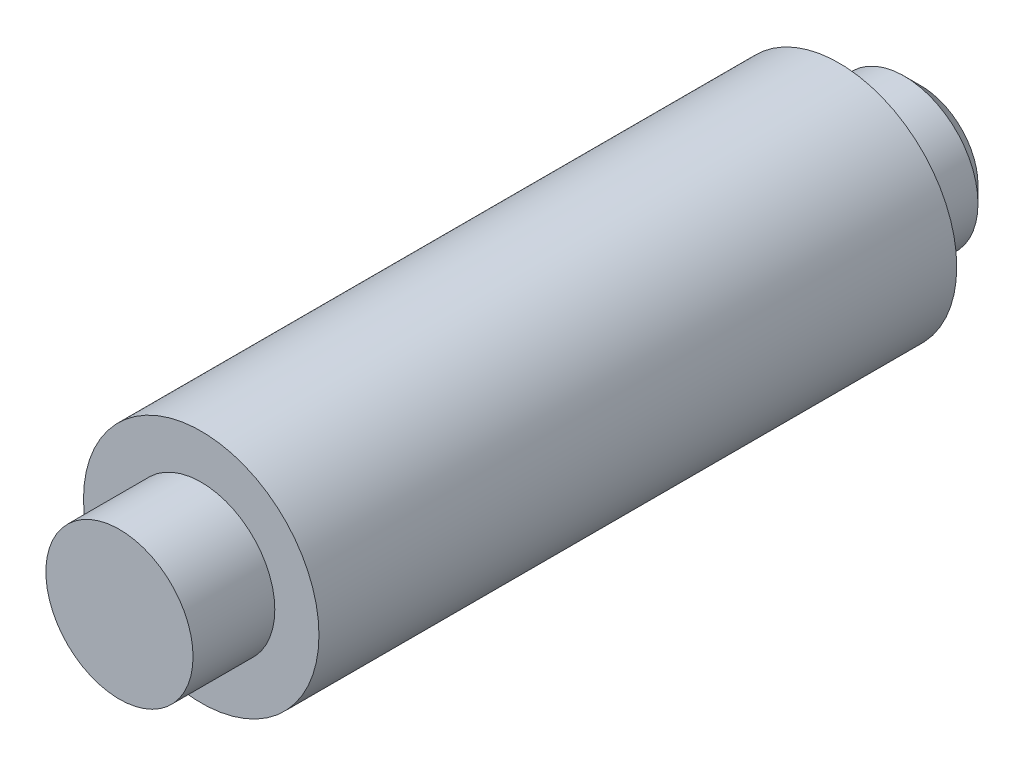
SolidWorks part; units mm, degrees
ref_plane "Front Plane" through (0, 0, 0) normal (0, 0, 1) x (1, 0, 0)
ref_plane "Top Plane" through (0, 0, 0) normal (0, 1, 0) x (1, 0, 0)
ref_plane "Right Plane" through (0, 0, 0) normal (1, 0, 0) x (0, 0, -1)
sketch "Sketch2" plane through (0, 0, 0) normal (0, 0, 1) x (1, 0, 0)
  circle A0 centre (0, 0) radius 1.25
  dimension "D1" = 2.5
sketch "Sketch3" plane through (0, 0, 0) normal (0, 0, 1) x (1, 0, 0)
  line L5 (-3.6, 3.6) -> (3.6, 3.6) construction
  line L6 (-3.6, 3.6) -> (-3.6, -3.6) construction
  line L7 (-3.6, -3.6) -> (3.6, -3.6) construction
  line L8 (3.6, 3.6) -> (3.6, -3.6) construction
  circle A0 centre (0, 0) radius 3.6
  point P4 (0, 3.6)
  point P6 (-3.6, 0)
  dimension "D1" = 7.2
extrude "Boss-Extrude1" add sketch "Sketch3" along normal blind 19.5
sketch "Sketch4" plane through (0, 0, 0) normal (0, 0, 1) x (1, 0, 0)
  circle A0 centre (0, 0) radius 2.25
  dimension "D1" = 4.5
extrude "Boss-Extrude2" add sketch "Sketch4" against normal blind 2.5
sketch "Sketch5" plane through (0, 0, 19.5) normal (0, 0, 1) x (1, 0, 0)
  circle A0 centre (0, 0) radius 2.25
  dimension "D1" = 4.5
extrude "Boss-Extrude3" add sketch "Sketch5" along normal blind 2.5
chamfer "Chamfer1" distance 0.5 angle 45 1 edges at (2.25, 0, -2.5)
equation "\"length\"=19.5"
equation "\"D1@Boss-Extrude1\"=\"length\""
equation "\"holer\"=4.5"
equation "\"D1@Sketch5\"=\"holer\""
equation "\"D1@Sketch4\"=\"holer\""
